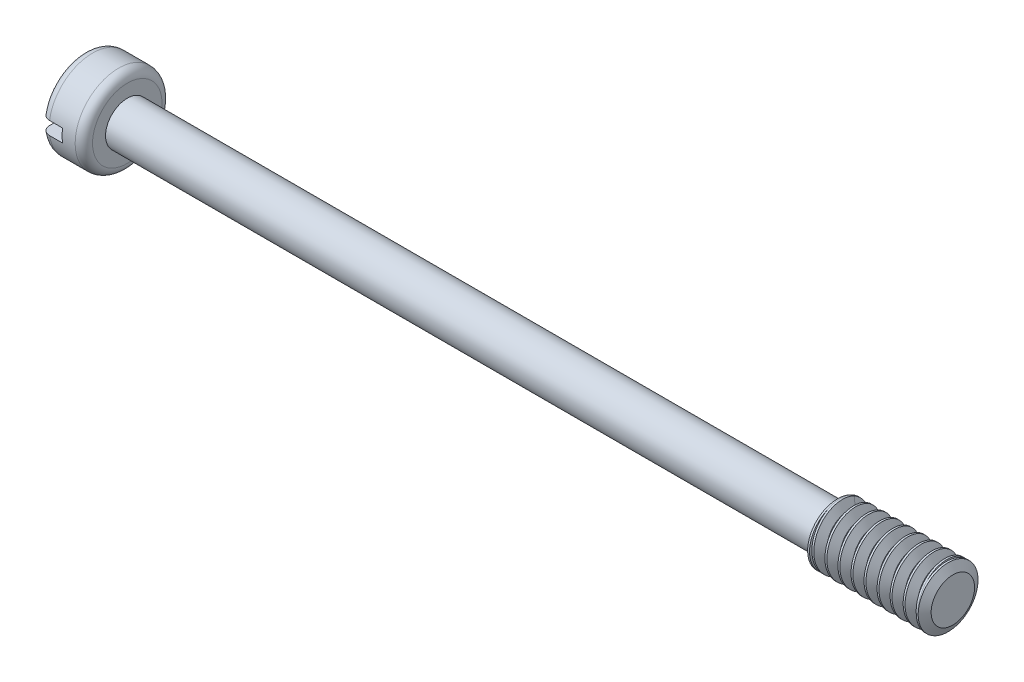
SolidWorks part; units mm, degrees
ref_plane "Front Plane" through (0, 0, 0) normal (0, 0, 1) x (1, 0, 0)
ref_plane "Top Plane" through (0, 0, 0) normal (0, 1, 0) x (1, 0, 0)
ref_plane "Right Plane" through (0, 0, 0) normal (1, 0, 0) x (0, 0, -1)
sketch "Sketch1" plane through (0, 0, 0) normal (0, 0, 1) x (1, 0, 0)
  line L0 (0, 0.8) -> (0, 0)
  line L1 (0, 0) -> (20, 0)
  line L2 (20, 0) -> (20, 0.5)
  line L3 (20, 0.5) -> (1, 0.5)
  line L4 (1, 0.5) -> (1, 0.8)
  line L5 (0.8, 1) -> (0.2, 1)
  arc A0 (0, 0.8) -> (0.2, 1) centre (0.2, 0.8) cw
  arc A1 (1, 0.8) -> (0.8, 1) centre (0.8, 0.8) ccw
  point P9 (0, 1)
  point P12 (1, 1)
  dimension "D5" = 0.2
  dimension "D1" = 0.5
  dimension "D2" = 1
  dimension "D3" = 1
  dimension "D4" = 20
revolve "Revolve1" add sketch "Sketch1" angle 360 about L1
thread "Thread1" pitch 0.35 method extrude profile "Thread Profile1" start angle 0, offset 0, length 2.5, pitch 0.3, diameter 1
ref_plane "Plane1" through (20, 0, 0.5) normal (0, -1, 0) x (0, 0, 1)
sketch "Thread Profile1" plane through (20, 0, 0.5) normal (0, -1, 0) x (0, 0, 1)
  line L0 (0, 0) -> (0, 0.35) construction
  line L1 (0, 0) -> (0.1894, 0.1094)
  line L2 (0.1894, 0.1094) -> (0.1894, 0.1531)
  line L3 (0.1894, 0.1531) -> (0, 0.2625)
  line L4 (0.1894, 0.1312) -> (0, 0.1312) construction
  line L11 (0, 0) -> (0, 0.2625)
  point P2 (0, 0)
  dimension "Pitch" = 0.35
  dimension "Profile_Angle" = 60
  dimension "Profile_Land" = 0.0437
  dimension "Profile_Height" = 0.1894
sketch "Sketch4" plane through (0, 0, 0) normal (0, -1, 0) x (1, 0, 0)
  line L4 (19.8906, 0.6894) -> (19.8469, 0.6894)
  line L5 (19.8469, 0.6894) -> (19.7375, 0.5)
  line L6 (19.7375, 0.5) -> (20, 0.5)
  line L7 (20, 0.5) -> (19.8906, 0.6894)
  line L8 (19.8906, 0.6894) -> (19.8469, 0.6894)
  line L9 (19.8469, 0.6894) -> (19.7375, 0.5)
  line L10 (19.7375, 0.5) -> (20, 0.5)
  line L11 (20, 0.5) -> (19.8906, 0.6894)
  dimension "D1" = 0
revolve "Revolve2" add sketch "Sketch4" angle 360 about axis through (0, 0, 0) along (-1, 0, 0)
sketch "Sketch5" plane through (0, 0, 0) normal (0, -0.5, -0.866) x (-1, 0, 0)
  line L4 (-17.3469, 0.6894) -> (-17.3906, 0.6894)
  line L5 (-17.3906, 0.6894) -> (-17.5, 0.5)
  line L6 (-17.5, 0.5) -> (-17.2375, 0.5)
  line L7 (-17.2375, 0.5) -> (-17.3469, 0.6894)
  line L8 (-17.3469, 0.6894) -> (-17.3906, 0.6894)
  line L9 (-17.3906, 0.6894) -> (-17.5, 0.5)
  line L10 (-17.5, 0.5) -> (-17.2375, 0.5)
  line L11 (-17.2375, 0.5) -> (-17.3469, 0.6894)
  dimension "D1" = 0
revolve "Revolve3" add sketch "Sketch5" angle 360 about axis through (0, 0, 0) along (-1, 0, 0)
sketch "Sketch6" plane through (0, 0, 0) normal (-1, 0, 0) x (0, 0, 1)
  line L1 (-0.15, -0.7858) -> (0.15, -0.7858)
  line L2 (-0.15, -0.7858) -> (-0.15, 0.7858)
  line L3 (-0.15, 0.7858) -> (0.15, 0.7858)
  line L4 (0.15, -0.7858) -> (0.15, 0.7858)
  line L5 (-0.15, -0.7858) -> (0.15, 0.7858) construction
  line L6 (-0.15, 0.7858) -> (0.15, -0.7858) construction
  line L7 (1, -0.15) -> (-1, -0.15)
  line L8 (1, -0.15) -> (1, 0.15)
  line L9 (1, 0.15) -> (-1, 0.15)
  line L10 (-1, -0.15) -> (-1, 0.15)
  line L11 (1, -0.15) -> (-1, 0.15) construction
  line L12 (1, 0.15) -> (-1, -0.15) construction
  circle A0 centre (0, 0) radius 1 construction
  circle A1 centre (0, 0) radius 0.8 construction
  point P0 (0, 0)
  point P5 (0, 0)
  point P13 (0, 0)
  dimension "D1" = 0.3
extrude "Cut-Extrude1" cut sketch "Sketch6" against normal blind 0.5 contours L7 L10 L9 L8 | L2 L3 L4 L1
